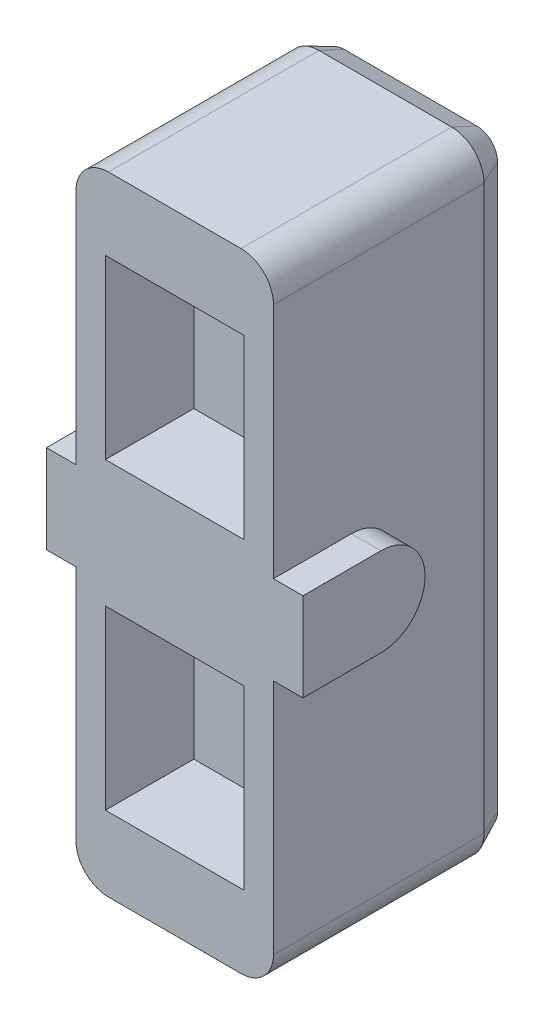
SolidWorks part; units mm, degrees
ref_plane "Plan de face" through (0, 0, 0) normal (0, 0, 1) x (1, 0, 0)
ref_plane "Plan de dessus" through (0, 0, 0) normal (0, 1, 0) x (1, 0, 0)
ref_plane "Plan de droite" through (0, 0, 0) normal (1, 0, 0) x (0, 0, -1)
sketch "Esquisse2" plane through (0, 0, 0) normal (0, 0, 1) x (1, 0, 0)
  line L1 (1.1, 0) -> (5.6, 0)
  line L2 (0, 1.1) -> (0, 20.2)
  line L3 (1.1, 21.3) -> (5.6, 21.3)
  line L4 (6.7, 1.1) -> (6.7, 20.2)
  arc A0 (5.6, 21.3) -> (6.7, 20.2) centre (5.6, 20.2) cw
  arc A1 (5.6, 0) -> (6.7, 1.1) centre (5.6, 1.1) ccw
  arc A2 (1.1, 0) -> (0, 1.1) centre (1.1, 1.1) cw
  arc A3 (0, 20.2) -> (1.1, 21.3) centre (1.1, 20.2) cw
  point P7 (6.7, 21.3)
  point P12 (0, 0)
  point P15 (0, 21.3)
  dimension "D3" = 1.1
  dimension "D1" = 6.7
  dimension "D2" = 21.3
extrude "Boss.-Extru.1" add sketch "Esquisse2" along normal blind 8
sketch "Esquisse3" plane through (0, 0, 8) normal (0, 0, 1) x (1, 0, 0)
  line L0 (0, 20.2) -> (0, 1.1) construction
  line L1 (1, 18.8) -> (5.7, 18.8)
  line L2 (1, 18.8) -> (1, 12.8)
  line L3 (1, 12.8) -> (5.7, 12.8)
  line L4 (5.7, 18.8) -> (5.7, 12.8)
  line L5 (6.7, 1.1) -> (6.7, 20.2) construction
  line L6 (5.6, 21.3) -> (1.1, 21.3) construction
  line L8 (1.1, 0) -> (5.6, 0) construction
  line L9 (1, 8.5) -> (5.7, 8.5)
  line L10 (1, 8.5) -> (1, 2.5)
  line L11 (1, 2.5) -> (5.7, 2.5)
  line L12 (5.7, 8.5) -> (5.7, 2.5)
  line L13 (-7.1761, 15.8) -> (15.2275, 15.8) construction
  dimension "D2" = 6
  dimension "D3" = 1
  dimension "D4" = 1
  dimension "D5" = 2.5
  dimension "D6" = 6
  dimension "D8" = 1
  dimension "D9" = 2.5
  dimension "D10" = 5.5
  dimension "D11" = 1
chamfer "Chanfrein1" distance 0.4 angle 65 8 edges at (3.35, 0, 0) (6.3778, 0.3222, 0) (0.3222, 0.3222, 0) (6.7, 10.65, 0) (0, 10.65, 0) (6.3778, 20.9778, 0) (0.3222, 20.9778, 0) (3.35, 21.3, 0) first distance on face at (3.35, 10.65, 0)
sketch "Esquisse5" plane through (0, 0, 0) normal (0, 0, 1) x (1, 0, 0)
  line L1 (1.54, 5.9) -> (5.1595, 5.9)
  line L2 (5.1595, 5.9) -> (3.3498, 1.9)
  line L3 (3.3498, 1.9) -> (1.54, 5.9)
  line L4 (3.3498, 3.3556) -> (2.47, 5.3)
  line L5 (2.47, 5.3) -> (4.2295, 5.3)
  line L6 (4.2295, 5.3) -> (3.3498, 3.3556)
  line L7 (5.6, 0.4) -> (1.1, 0.4) construction
  line L8 (1.54, 15.4) -> (5.16, 15.4)
  line L9 (5.16, 15.4) -> (3.35, 19.4)
  line L10 (3.35, 19.4) -> (1.54, 15.4)
  line L11 (2.4701, 16) -> (4.2299, 16)
  line L12 (4.2299, 16) -> (3.35, 17.9446)
  line L13 (3.35, 17.9446) -> (2.4701, 16)
  line L14 (1.1, 20.9) -> (5.6, 20.9) construction
  line L15 (0.4, 1.1) -> (0.4, 20.2) construction
  line L16 (6.3, 20.2) -> (6.3, 1.1) construction
  line L17 (6.3, 9.6541) -> (0.4, 9.6541) construction
  text T0 "RNG" font "Century Gothic" height 2.5
  dimension "D1" = 0.6
  dimension "D2" = 0.6
  dimension "D3" = 0.6
  dimension "D4" = 1.8098
  dimension "D5" = 1.8097
  dimension "D6" = 4
  dimension "D7" = 1.5
  dimension "D8" = 0.6
  dimension "D9" = 0.6
  dimension "D10" = 0.6
  dimension "D11" = 4
  dimension "D12" = 1.81
  dimension "D13" = 1.81
  dimension "D14" = 1.5
  dimension "D15" = 1.14
  dimension "D16" = 1.1405
  dimension "D17" = 1.14
extrude "Boss.-Extru.2" add sketch "Esquisse5<4>" against normal blind 0.2
sketch "Esquisse5<4>" plane through (0, 0, 0) normal (0, 0, 1) x (1, 0, 0) same geometry as "Esquisse5"
extrude "Enlèv. mat.-Extru.3" cut sketch "Esquisse5" along normal blind 0.2
extrude "Enlèv. mat.-Extru.4" cut sketch "Esquisse3" against normal blind 3
sketch "Esquisse6" plane through (0, 0, 0) normal (-1, 0, 0) x (0, 0, 1)
  line L0 (-8.8899, 10.65) -> (18.0179, 10.65) construction
  line L1 (8, 20.2) -> (0.8578, 20.2) construction
  line L2 (8, 1.1) -> (0.8578, 1.1) construction
  line L3 (0.8578, 20.2) -> (0.8578, 1.1) construction
  line L5 (5.3578, 12.15) -> (8, 12.15)
  line L6 (8, 1.1) -> (8, 20.2) construction
  line L7 (8, 12.15) -> (8, 9.15)
  line L8 (8, 9.15) -> (5.3578, 9.15)
  arc A0 (5.3578, 9.15) -> (5.3578, 12.15) centre (5.3578, 10.65) cw
  dimension "D4" = 1.5
  dimension "D1" = 9.55
  dimension "D2" = 9.55
  dimension "D3" = 0
  dimension "D5" = 4.5
extrude "Boss.-Extru.3" add sketch "Esquisse6" along normal blind 1 and the other way blind 7.7
